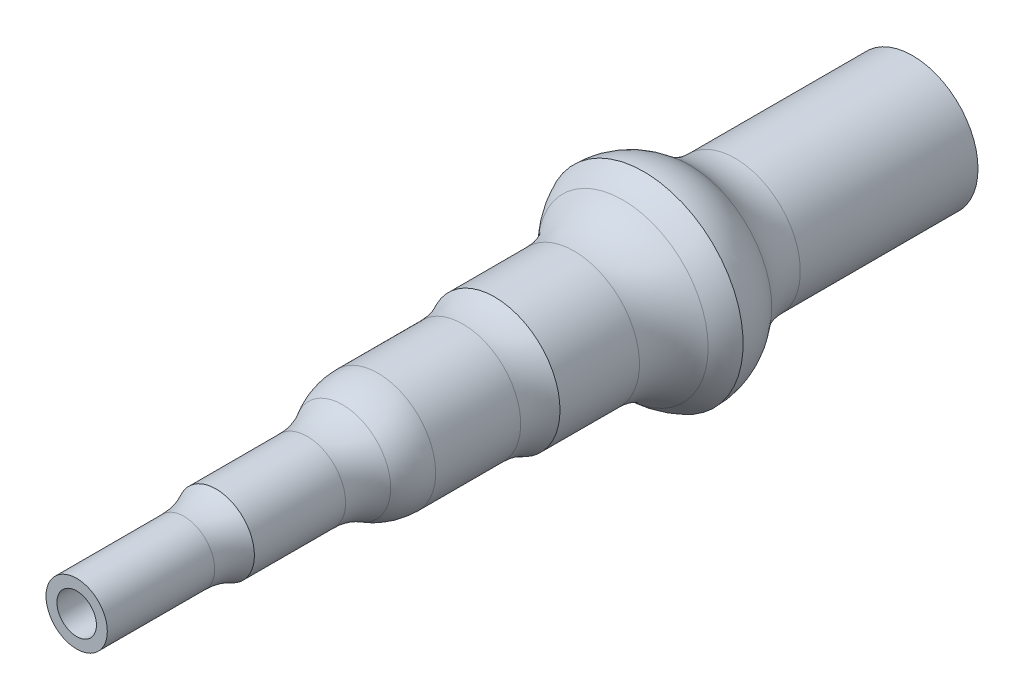
SolidWorks part; units mm, degrees
other "Markup1"
sketch "Sketch8" plane through (-7.1301, 7.1301, 0) normal (-0.3659, 0.3193, -0.8742) x (-0.9224, 0, 0.3861)
ref_plane "Front Plane" through (0, 0, 0) normal (0, 0, 1) x (1, 0, 0)
ref_plane "Top Plane" through (0, 0, 0) normal (0, 1, 0) x (1, 0, 0)
ref_plane "Right Plane" through (0, 0, 0) normal (1, 0, 0) x (0, 0, -1)
sketch "Sketch1" plane through (0, 0, 0) normal (0, 0, 1) x (1, 0, 0)
  circle A2 centre (0, 0) radius 2.2
  circle A3 centre (0, 0) radius 4.69
  dimension "D1" = 4.4
extrude "Boss-Extrude3" add sketch "Sketch1" along normal blind 30
sketch "Sketch3" plane through (0, 0, 30) normal (0, 0, 1) x (1, 0, 0)
  circle A0 centre (0, 0) radius 4.1433
  circle A1 centre (0, 0) radius 2.7398
extrude "Boss-Extrude4" add sketch "Sketch3" along normal blind 10
sketch "Sketch4" plane through (0, 0, 40) normal (0, 0, 1) x (1, 0, 0)
  circle A0 centre (0, 0) radius 2.7572
  circle A2 centre (0, 0) radius 1.674
extrude "Boss-Extrude5" add sketch "Sketch4" along normal blind 10
sketch "Sketch5" plane through (0, 0, 50) normal (0, 0, 1) x (1, 0, 0)
  circle A0 centre (0, 0) radius 2.2
  circle A1 centre (0, 0) radius 1.4177
  dimension "D1" = 4.4
extrude "Boss-Extrude6" add sketch "Sketch5" along normal blind 10
fillet "Fillet13" radius 5 1 edges at (1.4177, 0, 50)
fillet "Fillet15" radius 5 1 edges at (1.674, 0, 50)
fillet "Fillet16" radius 5 1 edges at (2.2, 0, 50)
fillet "Fillet17" radius 5 1 edges at (1.674, 0, 40)
fillet "Fillet18" radius 5 1 edges at (2.7572, 0, 40)
fillet "Fillet19" radius 5 1 edges at (2.7398, 0, 40)
fillet "Fillet20" radius 5 1 edges at (4.1433, 0, 40)
fillet "Fillet21" radius 5 1 edges at (4.1433, 0, 30)
sketch "Sketch6" plane through (0, 0, 0) normal (0, 0, -1) x (-1, 0, 0)
  circle A1 centre (0, 0) radius 7.1301
extrude "Boss-Extrude7" add sketch "Sketch6" along normal blind 5 from offset 20 offset against normal yes
sketch "Sketch7" plane through (0, 0, 0) normal (0, 0, -1) x (-1, 0, 0)
  circle A0 centre (0, 0) radius 3.7687
extrude "Cut-Extrude1" cut sketch "Sketch7" against normal blind 30
fillet "Fillet26" radius 5 1 edges at (-4.69, 0, 20)
fillet "Fillet27" radius 5 1 edges at (-7.1301, 0, 15)
fillet "Fillet28" radius 5 2 edges at (-7.1301, 0, 20) (-4.69, 0, 15)
fillet "Fillet29" radius 5 1 edges at (-2.7398, 0, 30)
fillet "Fillet30" radius 5 1 edges at (-3.7687, 0, 30)
